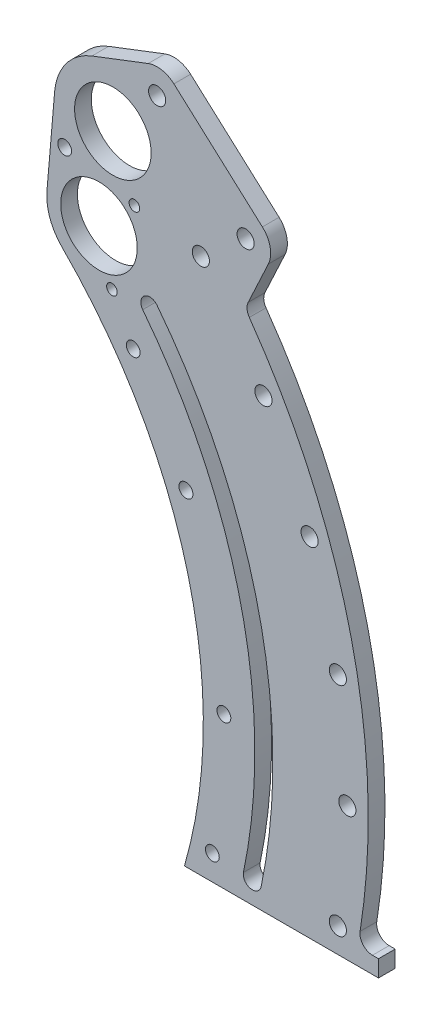
SolidWorks part; units mm, degrees
material "6061-T6 (SS)"
ref_plane "Front Plane" through (0, 0, 0) normal (0, 0, 1) x (1, 0, 0)
ref_plane "Top Plane" through (0, 0, 0) normal (0, 1, 0) x (1, 0, 0)
ref_plane "Right Plane" through (0, 0, 0) normal (1, 0, 0) x (0, 0, -1)
sketch "Sketch1" plane through (0, 0, 0) normal (0, 0, 1) x (1, 0, 0)
  line L0 (0, 0) -> (177.8, 0) construction
  line L1 (177.8, 0) -> (183.3563, 0) construction
  line L2 (0, 0) -> (191.1772, 6.6761) construction
  line L3 (0, 0) -> (182.7798, 182.7798) construction
  line L4 (184.7031, 10.1184) -> (184.959, 2.7905) construction
  line L5 (184.959, 2.7905) -> (191.4331, -0.6518) construction
  line L6 (191.4331, -0.6518) -> (197.6513, 3.2337) construction
  line L7 (197.6513, 3.2337) -> (197.3954, 10.5616) construction
  line L8 (197.3954, 10.5616) -> (190.9213, 14.0039) construction
  line L9 (190.9213, 14.0039) -> (184.7031, 10.1184) construction
  line L10 (156.6987, 109.7216) -> (0, 0) construction
  line L11 (0, 0) -> (176.7324, 73.2049) construction
  line L12 (183.3563, 0) -> (183.3563, -50.8) construction
  line L13 (176.1785, -50.8) -> (183.3563, -50.8) construction
  line L14 (0, 0) -> (186.7878, -41.275) construction
  line L15 (0, 0) -> (203.2, 0) construction
  line L16 (203.2, 0) -> (209.55, 0) construction
  line L17 (209.55, 0) -> (228.6, 0) construction
  line L18 (228.6, 0) -> (238.125, 0) construction
  line L19 (0, 0) -> (238.125, 0) construction
  line L20 (0, 0) -> (234.5073, 41.35) construction
  line L21 (176.1785, -50.8) -> (240.7615, -50.8)
  line L22 (0, 0) -> (238.125, 0) construction
  line L23 (0, 0) -> (234.5073, -41.35) construction
  line L24 (129.6524, 129.6524) -> (173.9925, 173.9925)
  line L25 (165.5338, 128.4903) -> (160.5177, 124.5966) construction
  line L26 (198.8628, -41.7593) -> (205.1195, -42.8625) construction
  arc A0 (183.3563, 0) -> (129.6524, 129.6524) centre (0, 0) ccw
  arc A1 (184.9438, 0) -> (130.775, 130.775) centre (0, 0) ccw construction
  circle A3 centre (191.1772, 6.6761) radius 6.35 construction
  circle A4 centre (191.1772, 6.6761) radius 2.6289
  circle A5 centre (156.6987, 109.7216) radius 2.6289
  circle A6 centre (176.7324, 73.2049) radius 2.667
  arc A7 (183.3563, 0) -> (176.1785, -50.8) centre (0, 0) cw
  circle A8 centre (186.7878, -41.275) radius 2.6289
  arc A9 (203.2, 0) -> (143.6841, 143.6841) centre (0, 0) ccw construction
  arc A10 (209.55, 0) -> (148.1742, 148.1742) centre (0, 0) ccw construction
  arc A11 (228.6, 0) -> (161.6446, 161.6446) centre (0, 0) ccw construction
  arc A12 (238.125, 0) -> (168.3798, 168.3798) centre (0, 0) ccw construction
  circle A13 centre (238.125, 0) radius 3.2639
  circle A14 centre (234.5073, 41.35) radius 3.2639
  circle A15 centre (223.7643, 81.4435) radius 3.2639
  circle A16 centre (206.2223, 119.0625) radius 3.2639
  circle A17 centre (182.4143, 153.0638) radius 3.2639
  arc A18 (240.7615, -50.8) -> (173.9925, 173.9925) centre (0, 0) ccw
  circle A19 centre (234.5073, -41.35) radius 3.2639
  arc A20 (209.55, 0) -> (165.5338, 128.4903) centre (0, 0) ccw construction
  arc A21 (160.5177, 124.5966) -> (203.2, 0) centre (0, 0) cw construction
  arc A22 (209.55, 0) -> (205.1195, -42.8625) centre (0, 0) cw construction
  arc A23 (203.2, 0) -> (198.8628, -41.7593) centre (0, 0) cw construction
  arc A24 (165.5338, 128.4903) -> (160.5177, 124.5966) centre (163.0257, 126.5435) ccw construction
  arc A25 (205.1195, -42.8625) -> (198.8628, -41.7593) centre (201.9911, -42.3109) cw construction
  arc A26 (202.946, 0) -> (198.6134, -41.711) centre (0, 0) cw
  arc A27 (205.3689, -42.9106) -> (198.6134, -41.711) centre (201.9911, -42.3109) cw
  arc A28 (209.804, 0) -> (205.3689, -42.9106) centre (0, 0) cw
  arc A29 (209.804, 0) -> (165.7345, 128.646) centre (0, 0) ccw
  arc A30 (165.7345, 128.646) -> (160.317, 124.4409) centre (163.0257, 126.5435) ccw
  arc A31 (160.317, 124.4409) -> (202.946, 0) centre (0, 0) cw
  point P9 (151.4971, 106.0794)
  point P20 (170.8657, 70.7749)
  point P27 (179.0372, -39.5623)
  dimension "D3" = 1.5875
  dimension "D4" = 12.7
  dimension "D6" = 5.2578
  dimension "D8" = 5.2578
  dimension "D12" = 5.334
  dimension "D14" = 50.8
  dimension "D15" = 5.2578
  dimension "D19" = 6.35
  dimension "D20" = 19.05
  dimension "D22" = 6.5278
  dimension "D26" = 7.9375
  dimension "D30" = 25.4
  dimension "D31" = 7.9375
  dimension "D33" = 183.3562
  dimension "D1" = 177.8
  dimension "D2" = 5.5562
  dimension "D5" = 2
  dimension "D7" = 45
  dimension "D9" = 6.35
  dimension "D10" = 10
  dimension "D11" = 22.5
  dimension "D13" = 6.35
  dimension "D16" = 9.525
  dimension "D17" = 7.9375
  dimension "D18" = 203.2
  dimension "D21" = 9.525
  dimension "D24" = 10
  dimension "D25" = 238.125
  dimension "D28" = 10
  dimension "D29" = 238.125
  dimension "D32" = 0.254
  dimension "D23" = 5
  dimension "D27" = 2
extrude "Boss-Extrude1" add sketch "Sketch1" along normal blind 6.35 contours L21 A18 L24 A0 A7 A19 A4 A5 A6 A8 A13 A14 A15 A16 A17 A22 A25 A23 A21 A24 A20 region at (184.0595, -26.0065, 0)
sketch "Sketch2" plane through (0, 0, 6.35) normal (0, 0, 1) x (1, 0, 0)
  line L0 (0, 0) -> (125.7236, 125.7236) construction
  line L1 (0, 0) -> (183.3562, 0) construction
  line L2 (125.7236, 125.7236) -> (143.6841, 143.6841) construction
  line L3 (129.6524, 129.6524) -> (173.9925, 173.9925) construction
  line L4 (143.6841, 143.6841) -> (148.964, 177.5652) construction
  line L6 (0, 0) -> (148.964, 177.5652) construction
  arc A0 (176.1785, -50.8) -> (129.6524, 129.6524) centre (0, 0) ccw construction
  circle A1 centre (143.6841, 143.6841) radius 14.5542
  circle A2 centre (143.6841, 143.6841) radius 25.4 construction
  circle A3 centre (143.6841, 143.6841) radius 11.43 construction
  circle A4 centre (143.6841, 143.6841) radius 19.05 construction
  circle A5 centre (148.964, 177.5652) radius 22.86 construction
  circle A6 centre (148.964, 177.5652) radius 14.5542
  dimension "D4" = 29.1084
  dimension "D5" = 50.8
  dimension "D6" = 22.86
  dimension "D7" = 38.1
  dimension "D8" = 45.72
  dimension "D9" = 231.775
  dimension "D10" = 29.1084
  dimension "D1" = 177.8
  dimension "D2" = 45
  dimension "D3" = 25.4
  dimension "D11" = 34.29
sketch "Sketch3" plane through (0, 0, 6.35) normal (0, 0, 1) x (1, 0, 0)
  line L0 (129.6524, 129.6524) -> (173.9925, 173.9925) construction
  line L1 (129.6524, 129.6524) -> (161.6446, 161.6446)
  line L4 (123.9121, 145.3706) -> (126.8194, 179.454)
  line L5 (161.6446, 161.6446) -> (173.9925, 173.9925)
  line L6 (0, 0) -> (199.4397, 167.3498) construction
  line L7 (0, 0) -> (183.3562, 0) construction
  line L9 (208.0723, 163.3243) -> (199.2435, 144.391)
  line L10 (148.964, 177.5652) -> (165.7989, 197.6325) construction
  line L11 (0, 0) -> (148.964, 177.5652) construction
  line L12 (140.998, 198.3135) -> (162.385, 206.5246)
  line L13 (172.1715, 204.7117) -> (205.8123, 174.429)
  line L14 (143.6841, 143.6841) -> (148.964, 177.5652) construction
  line L15 (146.324, 160.6246) -> (130.6383, 163.069) construction
  arc A1 (129.6524, 129.6524) -> (123.9121, 145.3706) centre (143.6841, 143.6841) cw
  arc A2 (140.998, 198.3135) -> (126.8194, 179.454) centre (148.964, 177.5652) ccw
  circle A3 centre (148.964, 177.5652) radius 14.5542
  circle A4 centre (199.4397, 167.3498) radius 3.2639
  arc A5 (208.0723, 163.3243) -> (205.8123, 174.429) centre (199.4397, 167.3498) ccw
  arc A7 (173.9925, 173.9925) -> (199.2435, 144.391) centre (0, 0) cw
  arc A8 (240.7615, -50.8) -> (173.9925, 173.9925) centre (0, 0) ccw construction
  circle A9 centre (165.7989, 197.6325) radius 9.525 construction
  circle A10 centre (148.964, 177.5652) radius 16.1417 construction
  circle A11 centre (165.7989, 197.6325) radius 3.2639
  arc A12 (162.385, 206.5246) -> (172.1715, 204.7117) centre (165.7989, 197.6325) cw
  circle A13 centre (130.6383, 163.069) radius 2.6289
  circle A14 centre (130.6383, 163.069) radius 3.9687 construction
  dimension "D1" = 25.4
  dimension "D2" = 29.1084
  dimension "D3" = 22.225
  dimension "D5" = 260.35
  dimension "D6" = 6.5278
  dimension "D7" = 9.525
  dimension "D8" = 25
  dimension "D9" = 19.05
  dimension "D10" = 1.5875
  dimension "D11" = 6.5278
  dimension "D12" = 9.525
  dimension "D14" = 5.2578
  dimension "D15" = 7.9375
  dimension "D4" = 40
  dimension "D13" = 26.1937
  dimension "D16" = 15.875
extrude "Boss-Extrude2" add sketch "Sketch3" against normal blind 6.35
sketch "Sketch4" plane through (0, 0, 6.35) normal (0, 0, 1) x (1, 0, 0)
  line L0 (143.6841, 143.6841) -> (157.1545, 157.1545) construction
  line L1 (125.7236, 125.7236) -> (143.6841, 143.6841) construction
  line L2 (143.6841, 143.6841) -> (148.6146, 125.2832) construction
  circle A0 centre (143.6841, 143.6841) radius 14.5542
  circle A1 centre (157.1545, 157.1545) radius 2.0193
  circle A2 centre (148.6146, 125.2832) radius 2.0193
  dimension "D1" = 29.1084
  dimension "D2" = 4.0386
  dimension "D4" = 4.0386
  dimension "D3" = 19.05
  dimension "D5" = 19.05
  dimension "D6" = 60
extrude "Cut-Extrude1" cut sketch "Sketch4" against normal through all
sketch "Sketch5" plane through (0, 0, 6.35) normal (0, 0, 1) x (1, 0, 0)
  line L0 (240.7615, -50.8) -> (249.9519, -50.8)
  line L1 (249.9519, -50.8) -> (249.9519, -44.45)
  line L2 (249.9519, -44.45) -> (242.0144, -44.45)
  arc A0 (240.7615, -50.8) -> (199.2435, 144.391) centre (0, 0) ccw construction
  arc A1 (242.9628, -38.9339) -> (199.2435, 144.391) centre (0, 0) ccw construction
  arc A2 (242.0144, -44.45) -> (242.9628, -38.9339) centre (0, 0) ccw construction
  arc A3 (240.7615, -50.8) -> (242.0144, -44.45) centre (0, 0) ccw
  dimension "D2" = 6.35
  dimension "D3" = 7.9375
extrude "Boss-Extrude3" add sketch "Sketch5" against normal blind 6.35
fillet "Fillet1" radius 4.7625 1 edges at (242.0144, -44.45, 3.175)
fillet "Fillet2" radius 4.7625 1 edges at (199.2435, 144.391, 3.175)
